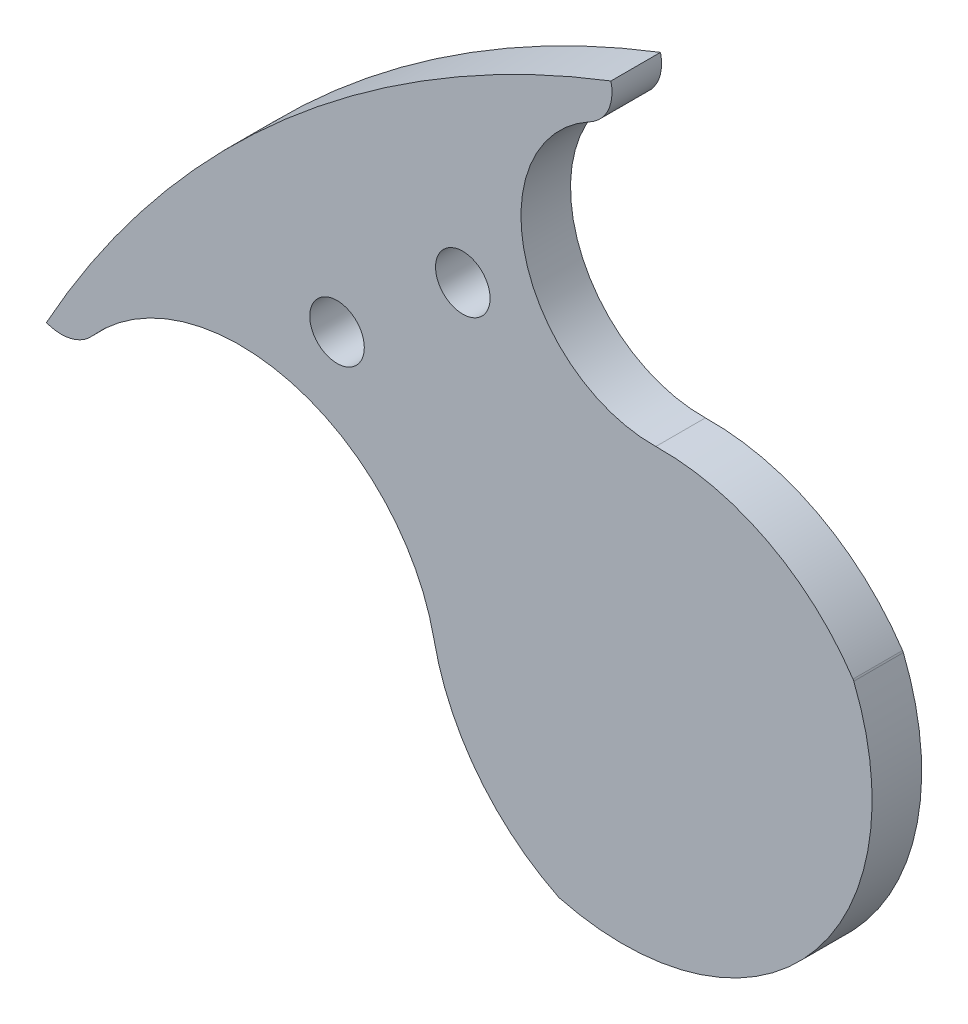
SolidWorks part; units mm, degrees
ref_plane "Front Plane" through (0, 0, 0) normal (1, 0, 0) x (0, 1, 0)
ref_plane "Top Plane" through (0, 0, 0) normal (0, 0, 1) x (0, 1, 0)
ref_plane "Right Plane" through (0, 0, 0) normal (0, 1, 0) x (-1, 0, 0)
ref_axis "Axis1" through (0, 0, 0) along (0, 1, 0)
sketch "Sketch4" plane through (0, 0, 0) normal (0, 0, 1) x (0, 1, 0)
  line L0 (40.3051, 40.3051) -> (0, 0) construction
  line L1 (0, 0) -> (46.6917, 32.6939) construction
  line L2 (0, 0) -> (19.8972, 0) construction
  circle A0 centre (40.3051, 40.3051) radius 1.65
  circle A1 centre (46.6917, 32.6939) radius 1.65
  dimension "D1" = 3.3
  dimension "D2" = 57
  dimension "D3" = 35
  dimension "D4" = 10
sketch "Sketch5" plane through (0, 0, 0) normal (0, 0, 1) x (0, 1, 0)
  line L0 (49.8899, 43.4375) -> (29.951, 20.7242) construction
  line L3 (19.1912, 26.037) -> (17.3979, 26.9224) construction
  line L5 (36.6129, 10.7433) -> (37.7232, 9.0798) construction
  line L6 (36.6129, 10.7433) -> (29.951, 20.7242) construction
  line L7 (29.951, 20.7242) -> (19.1912, 26.037) construction
  circle A0 centre (29.951, 20.7242) radius 11.875 construction
  arc A1 (19.1912, 26.037) -> (36.6129, 10.7433) centre (29.951, 20.7242) cw construction
  arc A3 (37.7232, 9.0798) -> (43.9481, 21.0113) centre (29.951, 20.7242) ccw
  arc A4 (61.7478, 23.7284) -> (32.0002, 57.8948) centre (0, 0) ccw
  arc A5 (61.7478, 23.7284) -> (58.9857, 24.9765) centre (61.1855, 26.1643) cw
  arc A6 (58.9857, 24.9765) -> (43.9481, 21.0113) centre (51.9464, 21.1754) ccw
  arc A7 (32.0002, 57.8948) -> (32.6709, 55.1375) centre (34.3356, 57.0027) ccw
  arc A8 (32.6709, 55.1375) -> (27.1132, 34.4335) centre (24.6807, 46.1844) cw
  arc A9 (27.1132, 34.4335) -> (17.3979, 26.9224) centre (29.951, 20.7242) ccw
  arc A10 (17.3979, 26.9224) -> (17.3625, 26.8278) centre (17.8462, 26.7011) ccw
  arc A12 (37.7232, 9.0798) -> (37.6339, 9.0324) centre (37.4457, 9.4956) cw
  arc A13 (17.3625, 26.8278) -> (37.6339, 9.0324) centre (31.9541, 23.006) ccw
  point P2 (29.951, 20.7242)
  point P6 (37.8676, 29.7423)
  point P7 (49.8899, 43.4375)
  dimension "D1" = 23.75
  dimension "D2" = 30.2234
  dimension "D4" = 150
  dimension "D5" = 12
  dimension "D6" = 2
  dimension "D7" = 2.5
  dimension "D8" = 2.5
  dimension "D9" = 8
  dimension "D10" = 12
  dimension "D11" = 0.5
  dimension "D12" = 66.15
  dimension "D13" = 0.5
  dimension "15" = 15.0838
extrude "Boss-Extrude1" add sketch "Sketch5" along normal blind 3
extrude "Cut-Extrude1" cut sketch "Sketch4" along normal through all
